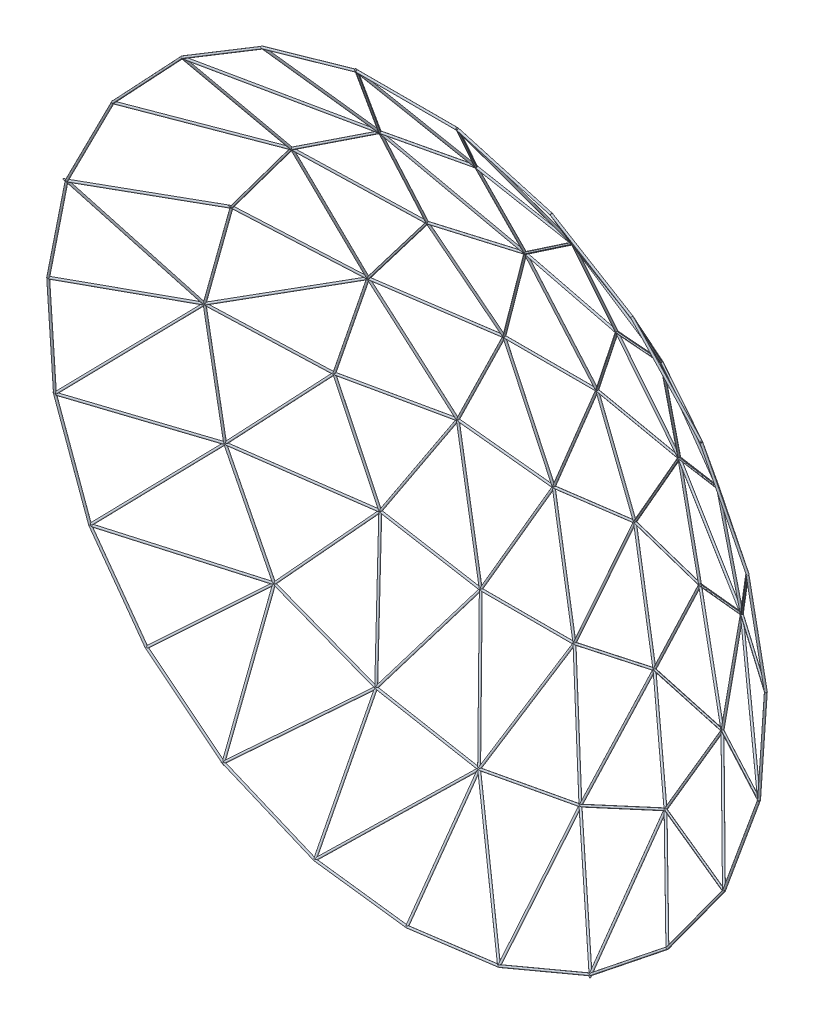
SolidWorks part; units mm, degrees
ref_plane "Front" through (0, 0, 0) normal (0, 0, 1) x (1, 0, 0)
ref_plane "Top" through (0, 0, 0) normal (0, 1, 0) x (1, 0, 0)
ref_plane "Right" through (0, 0, 0) normal (1, 0, 0) x (0, 0, -1)
sketch3d "3DSketch1"
  line L0 (70.2, 160.3, 72.9) -> (24.6, 173.3, 72.9)
  line L1 (24.6, 173.3, 72.9) -> (-24.6, 173.3, 72.9)
sketch3d "3DSketch2"
  line L0 (-24.6, 173.3, 72.9) -> (-70.2, 160.3, 72.9)
  line L1 (-70.2, 160.3, 72.9) -> (-46.9, 119.5, 39.2)
sketch3d "3DSketch3"
  line L0 (-46.9, 119.5, 39.2) -> (-24.6, 173.3, 72.9)
  line L1 (-24.6, 173.3, 72.9) -> (0, 128.4, 39.3)
sketch3d "3DSketch4"
  line L0 (0, 128.4, 39.3) -> (46.9, 119.5, 39.2)
  line L1 (46.9, 119.5, 39.2) -> (109.4, 136.6, 72.9)
sketch3d "3DSketch5"
  line L0 (109.4, 136.6, 72.9) -> (90, 90.9, 39)
  line L1 (90, 90.9, 39) -> (118.3, 52.6, 39.9)
sketch3d "3DSketch6"
  line L0 (118.3, 52.6, 39.9) -> (75.7, 32, 16.1)
  line L1 (75.7, 32, 16.1) -> (130.7, 6, 40.7)
sketch3d "3DSketch7"
  line L0 (130.7, 6, 40.7) -> (171.3, -36, 72.9)
  line L1 (171.3, -36, 72.9) -> (154.2, -82.8, 72.9)
sketch3d "3DSketch8"
  line L0 (154.2, -82.8, 72.9) -> (126.7, -120.7, 72.9)
  line L1 (154.2, -82.8, 72.9) -> (95.2, -93.3, 42.3)
sketch3d "3DSketch9"
  line L0 (95.2, -93.3, 42.3) -> (66.7, -60.1, 19.2)
  line L1 (66.7, -60.1, 19.2) -> (121, -48.1, 40.4)
sketch3d "3DSketch10"
  line L0 (121, -48.1, 40.4) -> (89, -13.2, 19.3)
  line L1 (89, -13.2, 19.3) -> (75.7, 32, 16.1)
sketch3d "3DSketch11"
  line L0 (75.7, 32, 16.1) -> (43.1, -16.8, 5.1)
  line L1 (43.1, -16.8, 5.1) -> (66.7, -60.1, 19.2)
sketch3d "3DSketch12"
  line L0 (66.7, -60.1, 19.2) -> (22.8, -73.6, 14.2)
  line L1 (22.8, -73.6, 14.2) -> (49.7, -116.5, 38.2)
sketch3d "3DSketch13"
  line L0 (49.7, -116.5, 38.2) -> (44.8, -169.2, 72.9)
  line L1 (44.8, -169.2, 72.9) -> (0, -175, 72.9)
sketch3d "3DSketch14"
  line L0 (0, -175, 72.9) -> (0, -126.1, 37.8)
  line L1 (0, -126.1, 37.8) -> (49.7, -116.5, 38.2)
sketch3d "3DSketch15"
  line L0 (49.7, -116.5, 38.2) -> (89.3, -150.5, 72.9)
  line L1 (89.3, -150.5, 72.9) -> (95.2, -93.3, 42.3)
sketch3d "3DSketch16"
  line L0 (95.2, -93.3, 42.3) -> (49.7, -116.5, 38.2)
  line L1 (49.7, -116.5, 38.2) -> (66.7, -60.1, 19.2)
sketch3d "3DSketch17"
  line L0 (66.7, -60.1, 19.2) -> (89, -13.2, 19.3)
  line L1 (89, -13.2, 19.3) -> (130.7, 6, 40.7)
sketch3d "3DSketch18"
  line L0 (130.7, 6, 40.7) -> (118.3, 52.6, 39.9)
  line L1 (130.7, 6, 40.7) -> (121, -48.1, 40.4)
sketch3d "3DSketch19"
  line L0 (121, -48.1, 40.4) -> (171.3, -36, 72.9)
  line L1 (171.3, -36, 72.9) -> (174.6, 11.2, 72.9)
sketch3d "3DSketch20"
  line L0 (174.6, 11.2, 72.9) -> (130.7, 6, 40.7)
  line L1 (130.7, 6, 40.7) -> (165.6, 56.6, 72.9)
sketch3d "3DSketch21"
  line L0 (165.6, 56.6, 72.9) -> (174.6, 11.2, 72.9)
  line L1 (154.2, -82.8, 72.9) -> (121, -48.1, 40.4)
sketch3d "3DSketch22"
  line L0 (121, -48.1, 40.4) -> (95.2, -93.3, 42.3)
  line L1 (95.2, -93.3, 42.3) -> (126.7, -120.7, 72.9)
sketch3d "3DSketch23"
  line L0 (126.7, -120.7, 72.9) -> (89.3, -150.5, 72.9)
  line L1 (89.3, -150.5, 72.9) -> (44.8, -169.2, 72.9)
sketch3d "3DSketch24"
  line L0 (44.8, -169.2, 72.9) -> (0, -126.1, 37.8)
  line L1 (0, -126.1, 37.8) -> (22.8, -73.6, 14.2)
sketch3d "3DSketch25"
  line L0 (22.8, -73.6, 14.2) -> (-22.8, -73.6, 14.2)
  line L1 (-22.8, -73.6, 14.2) -> (-43.1, -16.8, 5.1)
sketch3d "3DSketch26"
  line L0 (-43.1, -16.8, 5.1) -> (-66.7, -60.1, 19.2)
  line L1 (-66.7, -60.1, 19.2) -> (-49.7, -116.5, 38.2)
sketch3d "3DSketch27"
  line L0 (-49.7, -116.5, 38.2) -> (0, -126.1, 37.8)
  line L1 (0, -126.1, 37.8) -> (-44.8, -169.2, 72.9)
sketch3d "3DSketch28"
  line L0 (-44.8, -169.2, 72.9) -> (-49.7, -116.5, 38.2)
  line L1 (-49.7, -116.5, 38.2) -> (-22.8, -73.6, 14.2)
sketch3d "3DSketch29"
  line L0 (-22.8, -73.6, 14.2) -> (0, -25.4, 1.5)
  line L1 (0, -25.4, 1.5) -> (43.1, -16.8, 5.1)
sketch3d "3DSketch30"
  line L0 (43.1, -16.8, 5.1) -> (22.8, -73.6, 14.2)
  line L1 (22.8, -73.6, 14.2) -> (0, -25.4, 1.5)
sketch3d "3DSketch31"
  line L0 (0, -25.4, 1.5) -> (-22.6, 27.4, 3)
  line L1 (-22.6, 27.4, 3) -> (-43.1, -16.8, 5.1)
sketch3d "3DSketch32"
  line L0 (-43.1, -16.8, 5.1) -> (0, -25.4, 1.5)
  line L1 (0, -25.4, 1.5) -> (22.6, 27.4, 3)
sketch3d "3DSketch33"
  line L0 (22.6, 27.4, 3) -> (75.7, 32, 16.1)
  line L1 (75.7, 32, 16.1) -> (46.1, 70.6, 16.9)
sketch3d "3DSketch34"
  line L0 (46.1, 70.6, 16.9) -> (0, 80, 15.3)
  line L1 (46.1, 70.6, 16.9) -> (90, 90.9, 39)
sketch3d "3DSketch35"
  line L0 (90, 90.9, 39) -> (143.1, 100.8, 72.9)
  line L1 (143.1, 100.8, 72.9) -> (118.3, 52.6, 39.9)
sketch3d "3DSketch36"
  line L0 (118.3, 52.6, 39.9) -> (165.6, 56.6, 72.9)
  line L1 (165.6, 56.6, 72.9) -> (143.1, 100.8, 72.9)
sketch3d "3DSketch37"
  line L0 (143.1, 100.8, 72.9) -> (109.4, 136.6, 72.9)
  line L1 (109.4, 136.6, 72.9) -> (70.2, 160.3, 72.9)
sketch3d "3DSketch38"
  line L0 (70.2, 160.3, 72.9) -> (46.9, 119.5, 39.2)
  line L1 (0, 128.4, 39.3) -> (0, 80, 15.3)
sketch3d "3DSketch39"
  line L0 (0, 80, 15.3) -> (-46.1, 70.6, 16.9)
  line L1 (-46.1, 70.6, 16.9) -> (-46.9, 119.5, 39.2)
sketch3d "3DSketch40"
  line L0 (-46.9, 119.5, 39.2) -> (0, 80, 15.3)
  line L1 (0, 80, 15.3) -> (46.9, 119.5, 39.2)
sketch3d "3DSketch41"
  line L0 (46.9, 119.5, 39.2) -> (46.1, 70.6, 16.9)
  line L1 (46.1, 70.6, 16.9) -> (22.6, 27.4, 3)
sketch3d "3DSketch42"
  line L0 (22.6, 27.4, 3) -> (43.1, -16.8, 5.1)
  line L1 (43.1, -16.8, 5.1) -> (89, -13.2, 19.3)
sketch3d "3DSketch43"
  line L0 (75.7, 32, 16.1) -> (90, 90.9, 39)
  line L1 (90, 90.9, 39) -> (46.9, 119.5, 39.2)
sketch3d "3DSketch44"
  line L0 (46.9, 119.5, 39.2) -> (24.6, 173.3, 72.9)
  line L1 (24.6, 173.3, 72.9) -> (0, 128.4, 39.3)
sketch3d "3DSketch45"
  line L0 (0, 128.4, 39.3) -> (-46.9, 119.5, 39.2)
  line L1 (-46.1, 70.6, 16.9) -> (-75.7, 32, 16.1)
sketch3d "3DSketch46"
  line L0 (-75.7, 32, 16.1) -> (-89, -13.2, 19.3)
  line L1 (-75.7, 32, 16.1) -> (-22.6, 27.4, 3)
sketch3d "3DSketch47"
  line L0 (-22.6, 27.4, 3) -> (22.6, 27.4, 3)
  line L1 (22.6, 27.4, 3) -> (0, 80, 15.3)
sketch3d "3DSketch48"
  line L0 (0, 80, 15.3) -> (-22.6, 27.4, 3)
  line L1 (-22.6, 27.4, 3) -> (-46.1, 70.6, 16.9)
sketch3d "3DSketch49"
  line L0 (-46.1, 70.6, 16.9) -> (-90, 90.9, 39)
  line L1 (-90, 90.9, 39) -> (-75.7, 32, 16.1)
sketch3d "3DSketch50"
  line L0 (-75.7, 32, 16.1) -> (-43.1, -16.8, 5.1)
  line L1 (-43.1, -16.8, 5.1) -> (-89, -13.2, 19.3)
sketch3d "3DSketch51"
  line L0 (-89, -13.2, 19.3) -> (-66.7, -60.1, 19.2)
  line L1 (-66.7, -60.1, 19.2) -> (-95.2, -93.3, 42.3)
sketch3d "3DSketch52"
  line L0 (-95.2, -93.3, 42.3) -> (-89.3, -150.5, 72.9)
  line L1 (-89.3, -150.5, 72.9) -> (-126.7, -120.7, 72.9)
sketch3d "3DSketch53"
  line L0 (-126.7, -120.7, 72.9) -> (-95.2, -93.3, 42.3)
  line L1 (-95.2, -93.3, 42.3) -> (-49.7, -116.5, 38.2)
sketch3d "3DSketch54"
  line L0 (-49.7, -116.5, 38.2) -> (-89.3, -150.5, 72.9)
  line L1 (-89.3, -150.5, 72.9) -> (-44.8, -169.2, 72.9)
sketch3d "3DSketch55"
  line L0 (-44.8, -169.2, 72.9) -> (0, -175, 72.9)
  line L1 (0, -126.1, 37.8) -> (-22.8, -73.6, 14.2)
sketch3d "3DSketch56"
  line L0 (-22.8, -73.6, 14.2) -> (-66.7, -60.1, 19.2)
  line L1 (-66.7, -60.1, 19.2) -> (-121, -48.1, 40.4)
sketch3d "3DSketch57"
  line L0 (-121, -48.1, 40.4) -> (-171.3, -36, 72.9)
  line L1 (-171.3, -36, 72.9) -> (-154.2, -82.8, 72.9)
sketch3d "3DSketch58"
  line L0 (-171.3, -36, 72.9) -> (-174.6, 11.2, 72.9)
  line L1 (-174.6, 11.2, 72.9) -> (-165.6, 56.6, 72.9)
sketch3d "3DSketch59"
  line L0 (-165.6, 56.6, 72.9) -> (-143.1, 100.8, 72.9)
  line L1 (-143.1, 100.8, 72.9) -> (-90, 90.9, 39)
sketch3d "3DSketch60"
  line L0 (-90, 90.9, 39) -> (-46.9, 119.5, 39.2)
  line L1 (-46.9, 119.5, 39.2) -> (-109.4, 136.6, 72.9)
sketch3d "3DSketch61"
  line L0 (-109.4, 136.6, 72.9) -> (-90, 90.9, 39)
  line L1 (-90, 90.9, 39) -> (-118.3, 52.6, 39.9)
sketch3d "3DSketch62"
  line L0 (-118.3, 52.6, 39.9) -> (-130.7, 6, 40.7)
  line L1 (-118.3, 52.6, 39.9) -> (-75.7, 32, 16.1)
sketch3d "3DSketch63"
  line L0 (-75.7, 32, 16.1) -> (-130.7, 6, 40.7)
  line L1 (-130.7, 6, 40.7) -> (-174.6, 11.2, 72.9)
sketch3d "3DSketch64"
  line L0 (-171.3, -36, 72.9) -> (-130.7, 6, 40.7)
  line L1 (-130.7, 6, 40.7) -> (-121, -48.1, 40.4)
sketch3d "3DSketch65"
  line L0 (-121, -48.1, 40.4) -> (-95.2, -93.3, 42.3)
  line L1 (-95.2, -93.3, 42.3) -> (-154.2, -82.8, 72.9)
sketch3d "3DSketch66"
  line L0 (-154.2, -82.8, 72.9) -> (-126.7, -120.7, 72.9)
  line L1 (-154.2, -82.8, 72.9) -> (-121, -48.1, 40.4)
sketch3d "3DSketch67"
  line L0 (-121, -48.1, 40.4) -> (-89, -13.2, 19.3)
  line L1 (-89, -13.2, 19.3) -> (-130.7, 6, 40.7)
sketch3d "3DSketch68"
  line L0 (-130.7, 6, 40.7) -> (-165.6, 56.6, 72.9)
  line L1 (-165.6, 56.6, 72.9) -> (-118.3, 52.6, 39.9)
sketch3d "3DSketch69"
  line L0 (-118.3, 52.6, 39.9) -> (-143.1, 100.8, 72.9)
  line L1 (-143.1, 100.8, 72.9) -> (-109.4, 136.6, 72.9)
sketch3d "3DSketch70"
  line L0 (-109.4, 136.6, 72.9) -> (-70.2, 160.3, 72.9)
sweep "Sweep1" add path "3DSketch1" circular profile diameter 1 parameters "D3"=1
sweep "Sweep2" add path "3DSketch2" circular profile diameter 1 parameters "D3"=1
sweep "Sweep3" add path "3DSketch3" circular profile diameter 1 parameters "D3"=1
sweep "Sweep4" add path "3DSketch4" circular profile diameter 1 parameters "D3"=1
sweep "Sweep5" add path "3DSketch5" circular profile diameter 1 parameters "D3"=1
sweep "Sweep6" add path "3DSketch6" circular profile diameter 1 parameters "D3"=1
sweep "Sweep7" add path "3DSketch7" circular profile diameter 1 parameters "D3"=1
sweep "Sweep8" add path "3DSketch8" circular profile diameter 1 parameters "D3"=1
sweep "Sweep9" add path "3DSketch9" circular profile diameter 1 parameters "D3"=1
sweep "Sweep10" add path "3DSketch10" circular profile diameter 1 parameters "D3"=1
sweep "Sweep11" add path "3DSketch11" circular profile diameter 1 parameters "D3"=1
sweep "Sweep12" add path "3DSketch12" circular profile diameter 1 parameters "D3"=1
sweep "Sweep13" add path "3DSketch13" circular profile diameter 1 parameters "D3"=1
sweep "Sweep14" add path "3DSketch14" circular profile diameter 1 parameters "D3"=1
sweep "Sweep15" add path "3DSketch15" circular profile diameter 1 parameters "D3"=1
sweep "Sweep16" add path "3DSketch16" circular profile diameter 1 parameters "D3"=1
sweep "Sweep17" add path "3DSketch17" circular profile diameter 1 parameters "D3"=1
sweep "Sweep18" add path "3DSketch18" circular profile diameter 1 parameters "D3"=1
sweep "Sweep19" add path "3DSketch19" circular profile diameter 1 parameters "D3"=1
sweep "Sweep20" add path "3DSketch20" circular profile diameter 1 parameters "D3"=1
sweep "Sweep21" add path "3DSketch22" circular profile diameter 1 parameters "D3"=1
sweep "Sweep22" add path "3DSketch23" circular profile diameter 1 parameters "D3"=1
sweep "Sweep23" add path "3DSketch24" circular profile diameter 1 parameters "D3"=1
sweep "Sweep24" add path "3DSketch25" circular profile diameter 1 parameters "D3"=1
sweep "Sweep25" add path "3DSketch26" circular profile diameter 1 parameters "D3"=1
sweep "Sweep26" add path "3DSketch27" circular profile diameter 1 parameters "D3"=1
sweep "Sweep27" add path "3DSketch28" circular profile diameter 1 parameters "D3"=1
sweep "Sweep28" add path "3DSketch29" circular profile diameter 1 parameters "D3"=1
sweep "Sweep29" add path "3DSketch30" circular profile diameter 1 parameters "D3"=1
sweep "Sweep30" add path "3DSketch31" circular profile diameter 1 parameters "D3"=1
sweep "Sweep31" add path "3DSketch32" circular profile diameter 1 parameters "D3"=1
sweep "Sweep32" add path "3DSketch33" circular profile diameter 1 parameters "D3"=1
sweep "Sweep33" add path "3DSketch34" circular profile diameter 1 parameters "D3"=1
sweep "Sweep34" add path "3DSketch35" circular profile diameter 1 parameters "D3"=1
sweep "Sweep35" add path "3DSketch36" circular profile diameter 1 parameters "D3"=1
sweep "Sweep36" add path "3DSketch37" circular profile diameter 1 parameters "D3"=1
sweep "Sweep37" add path "3DSketch39" circular profile diameter 1 parameters "D3"=1
sweep "Sweep38" add path "3DSketch40" circular profile diameter 1 parameters "D3"=1
sweep "Sweep39" add path "3DSketch41" circular profile diameter 1 parameters "D3"=1
sweep "Sweep40" add path "3DSketch42" circular profile diameter 1 parameters "D3"=1
sweep "Sweep41" add path "3DSketch43" circular profile diameter 1 parameters "D3"=1
sweep "Sweep42" add path "3DSketch44" circular profile diameter 1 parameters "D3"=1
sweep "Sweep43" add path "3DSketch46" circular profile diameter 1 parameters "D3"=1
sweep "Sweep44" add path "3DSketch47" circular profile diameter 1 parameters "D3"=1
sweep "Sweep45" add path "3DSketch48" circular profile diameter 1 parameters "D3"=1
sweep "Sweep46" add path "3DSketch49" circular profile diameter 1 parameters "D3"=1
sweep "Sweep47" add path "3DSketch50" circular profile diameter 1 parameters "D3"=1
sweep "Sweep48" add path "3DSketch51" circular profile diameter 1 parameters "D3"=1
sweep "Sweep49" add path "3DSketch52" circular profile diameter 1 parameters "D3"=1
sweep "Sweep50" add path "3DSketch53" circular profile diameter 1 parameters "D3"=1
sweep "Sweep51" add path "3DSketch54" circular profile diameter 1 parameters "D3"=1
sweep "Sweep52" add path "3DSketch56" circular profile diameter 1 parameters "D3"=1
sweep "Sweep53" add path "3DSketch57" circular profile diameter 1 parameters "D3"=1
sweep "Sweep54" add path "3DSketch58" circular profile diameter 1 parameters "D3"=1
sweep "Sweep55" add path "3DSketch59" circular profile diameter 1 parameters "D3"=1
sweep "Sweep56" add path "3DSketch60" circular profile diameter 1 parameters "D3"=1
sweep "Sweep57" add path "3DSketch61" circular profile diameter 1 parameters "D3"=1
sweep "Sweep58" add path "3DSketch62" circular profile diameter 1 parameters "D3"=1
sweep "Sweep59" add path "3DSketch63" circular profile diameter 1 parameters "D3"=1
sweep "Sweep60" add path "3DSketch64" circular profile diameter 1 parameters "D3"=1
sweep "Sweep61" add path "3DSketch65" circular profile diameter 1 parameters "D3"=1
sweep "Sweep62" add path "3DSketch66" circular profile diameter 1 parameters "D3"=1
sweep "Sweep63" add path "3DSketch67" circular profile diameter 1 parameters "D3"=1
sweep "Sweep64" add path "3DSketch68" circular profile diameter 1 parameters "D3"=1
sweep "Sweep65" add path "3DSketch69" circular profile diameter 1 parameters "D3"=1
sweep "Sweep66" add path "3DSketch70" circular profile diameter 1 parameters "D3"=1
sweep "Sweep67" add path "3DSketch21" circular profile diameter 1 parameters "D3"=1
sweep "Sweep68" add path "3DSketch21<3>" circular profile diameter 1 parameters "D3"=1
sketch3d "3DSketch21<3>" same geometry as "3DSketch21"
sweep "Sweep69" add path "3DSketch38" circular profile diameter 1 parameters "D3"=1
sweep "Sweep70" add path "3DSketch38<3>" circular profile diameter 1 parameters "D3"=1
sketch3d "3DSketch38<3>" same geometry as "3DSketch38"
sweep "Sweep71" add path "3DSketch45" circular profile diameter 1 parameters "D3"=1
sweep "Sweep72" add path "3DSketch45<3>" circular profile diameter 1 parameters "D3"=1
sketch3d "3DSketch45<3>" same geometry as "3DSketch45"
sweep "Sweep73" add path "3DSketch55" circular profile diameter 1 parameters "D3"=1
sweep "Sweep74" add path "3DSketch55<3>" circular profile diameter 1 parameters "D3"=1
sketch3d "3DSketch55<3>" same geometry as "3DSketch55"
equation "\"wirediam\"=1"
equation "\"D3@Sweep1\"=\"wirediam\""
equation "\"D3@Sweep2\"=\"wirediam\""
equation "\"D3@Sweep3\"=\"wirediam\""
equation "\"D3@Sweep4\"=\"wirediam\""
equation "\"D3@Sweep5\"=\"wirediam\""
equation "\"D3@Sweep6\"=\"wirediam\""
equation "\"D3@Sweep7\"=\"wirediam\""
equation "\"D3@Sweep8\"=\"wirediam\""
equation "\"D3@Sweep9\"=\"wirediam\""
equation "\"D3@Sweep10\"=\"wirediam\""
equation "\"D3@Sweep11\"=\"wirediam\""
equation "\"D3@Sweep12\"=\"wirediam\""
equation "\"D3@Sweep13\"=\"wirediam\""
equation "\"D3@Sweep14\"=\"wirediam\""
equation "\"D3@Sweep15\"=\"wirediam\""
equation "\"D3@Sweep16\"=\"wirediam\""
equation "\"D3@Sweep17\"=\"wirediam\""
equation "\"D3@Sweep18\"=\"wirediam\""
equation "\"D3@Sweep19\"=\"wirediam\""
equation "\"D3@Sweep20\"=\"wirediam\""
equation "\"D3@Sweep21\"=\"wirediam\""
equation "\"D3@Sweep22\"=\"wirediam\""
equation "\"D3@Sweep23\"=\"wirediam\""
equation "\"D3@Sweep24\"=\"wirediam\""
equation "\"D3@Sweep25\"=\"wirediam\""
equation "\"D3@Sweep26\"=\"wirediam\""
equation "\"D3@Sweep27\"=\"wirediam\""
equation "\"D3@Sweep28\"=\"wirediam\""
equation "\"D3@Sweep29\"=\"wirediam\""
equation "\"D3@Sweep30\"=\"wirediam\""
equation "\"D3@Sweep31\"=\"wirediam\""
equation "\"D3@Sweep32\"=\"wirediam\""
equation "\"D3@Sweep33\"=\"wirediam\""
equation "\"D3@Sweep34\"=\"wirediam\""
equation "\"D3@Sweep35\"=\"wirediam\""
equation "\"D3@Sweep36\"=\"wirediam\""
equation "\"D3@Sweep37\"=\"wirediam\""
equation "\"D3@Sweep38\"=\"wirediam\""
equation "\"D3@Sweep39\"=\"wirediam\""
equation "\"D3@Sweep40\"=\"wirediam\""
equation "\"D3@Sweep41\"=\"wirediam\""
equation "\"D3@Sweep42\"=\"wirediam\""
equation "\"D3@Sweep43\"=\"wirediam\""
equation "\"D3@Sweep44\"=\"wirediam\""
equation "\"D3@Sweep45\"=\"wirediam\""
equation "\"D3@Sweep46\"=\"wirediam\""
equation "\"D3@Sweep47\"=\"wirediam\""
equation "\"D3@Sweep48\"=\"wirediam\""
equation "\"D3@Sweep49\"=\"wirediam\""
equation "\"D3@Sweep50\"=\"wirediam\""
equation "\"D3@Sweep51\"=\"wirediam\""
equation "\"D3@Sweep52\"=\"wirediam\""
equation "\"D3@Sweep53\"=\"wirediam\""
equation "\"D3@Sweep54\"=\"wirediam\""
equation "\"D3@Sweep55\"=\"wirediam\""
equation "\"D3@Sweep56\"=\"wirediam\""
equation "\"D3@Sweep57\"=\"wirediam\""
equation "\"D3@Sweep58\"=\"wirediam\""
equation "\"D3@Sweep59\"=\"wirediam\""
equation "\"D3@Sweep60\"=\"wirediam\""
equation "\"D3@Sweep61\"=\"wirediam\""
equation "\"D3@Sweep62\"=\"wirediam\""
equation "\"D3@Sweep63\"=\"wirediam\""
equation "\"D3@Sweep64\"=\"wirediam\""
equation "\"D3@Sweep65\"=\"wirediam\""
equation "\"D3@Sweep66\"=\"wirediam\""
equation "\"D3@Sweep67\"=\"wirediam\""
equation "\"D3@Sweep68\"=\"wirediam\""
equation "\"D3@Sweep69\"=\"wirediam\""
equation "\"D3@Sweep70\"=\"wirediam\""
equation "\"D3@Sweep71\"=\"wirediam\""
equation "\"D3@Sweep72\"=\"wirediam\""
equation "\"D3@Sweep73\"=\"wirediam\""
equation "\"D3@Sweep74\"=\"wirediam\""
